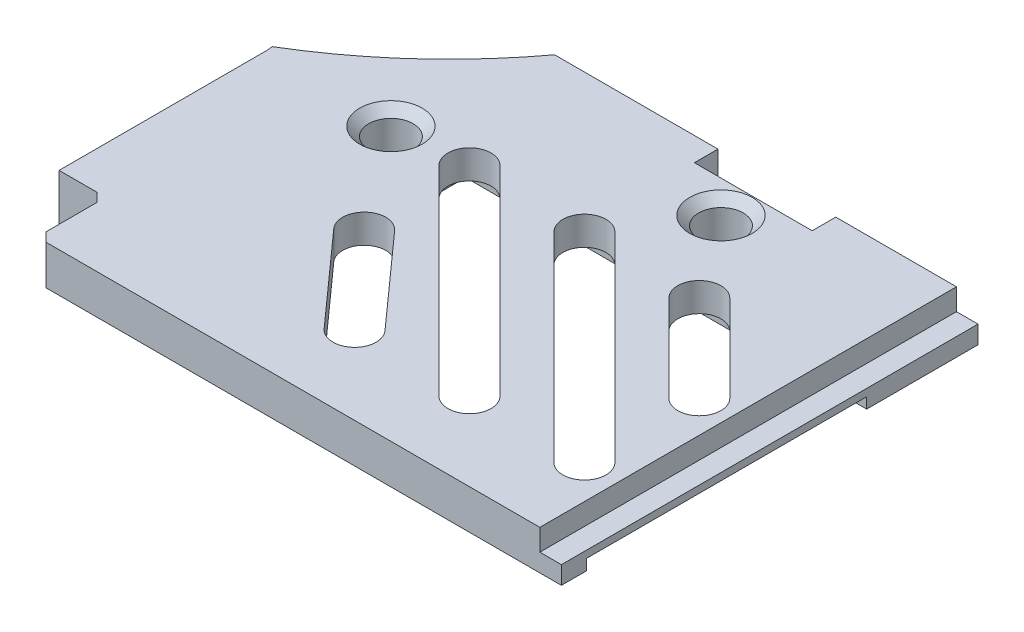
SolidWorks part; units mm, degrees
material "PPS"
ref_plane "前视基准面" through (0, 0, 0) normal (0, 0, 1) x (1, 0, 0)
ref_plane "上视基准面" through (0, 0, 0) normal (0, 1, 0) x (1, 0, 0)
ref_plane "右视基准面" through (0, 0, 0) normal (1, 0, 0) x (0, 0, -1)
sketch "基座草图-前" plane through (0, 0, 0) normal (0, 1, 0) x (1, 0, 0)
  line L2 (-24.7152, 2.0807) -> (-24.5, 0.3125)
  line L6 (-22.5, -14.2499) -> (-22.5, -7.2636)
  line L8 (-22.5, -7.2636) -> (-24.5, -7.2636)
  line L9 (-24.5, -7.2636) -> (-24.5, 0.3125)
  line L10 (-24.5, 0.3125) -> (-25.1116, 5.3379) construction
  line L12 (-26.5, 1.2398) -> (-26.5, -14.2499)
  line L13 (-26.5, -14.2499) -> (-22.5, -14.2499)
  line L16 (-4.1009, 11.812) -> (-4.1009, 8.358) construction
  line L17 (-4.1009, 8.358) -> (4.1009, 8.358)
  line L18 (4.1009, 8.358) -> (4.1009, 11.8106) construction
  line L19 (-16.253, 10) -> (-4.1009, 10)
  line L20 (-4.1009, 10) -> (-4.1009, 8.358)
  line L21 (4.1009, 8.358) -> (4.1009, 10)
  line L22 (0, 0.0001) -> (0, -23.6618) construction
  line L24 (4.1009, 10) -> (12.5, 10)
  line L25 (12.5, 10) -> (12.5, -14.2499)
  line L26 (12.5, -14.2499) -> (-26.5, -14.2499)
  arc A1 (-26.5, 2.4898) -> (-24.8662, 3.3216) centre (-28.6129, 8.6608) ccw construction
  arc A3 (-25.1116, 5.3379) -> (-57.77, 17.2644) centre (-45.4537, 0.3125) ccw construction
  arc A4 (-26.5, 1.2398) -> (-24.7152, 2.0807) centre (-28.3556, 7.493) ccw
  arc A5 (-17.503, 10) -> (-24.8662, 3.3216) centre (-44.5319, 32.4021) cw
  arc A6 (-16.253, 10) -> (-24.7152, 2.0807) centre (-44.1427, 31.321) cw
  circle A7 centre (0, 6.108) radius 1.55
  circle A8 centre (-16.866, 0) radius 1.55
  dimension "D1" = 1.25
  dimension "D2" = 1.25
  dimension "D3" = 1.25
  dimension "D4" = 16.866
  dimension "D5" = 12.5
  dimension "D6" = 9.9999
  dimension "D7" = 14.25
  dimension "D8" = 22.5
  dimension "D9" = 26.5
  dimension "D10" = 24.5
  dimension "D11" = 7.2637
extrude "基座-前" add sketch "基座草图-前" along normal blind 2.75 contours L19 A6 L2 L9 L8 L6 L26 L25 L24 L21 L17 L20 A8 A7 region at (-5.0831, 0, 2.6655)
sketch "基座草图-后" plane through (0, 0, 0) normal (0, 1, 0) x (1, 0, 0)
  line L0 (-22.5, -14.2499) -> (-22.5, -18.9999)
  line L1 (-22.5, -18.9999) -> (12.5, -18.9999)
  line L2 (12.5, -18.9999) -> (12.5, -14.2499)
  line L3 (12.5, 10) -> (12.5, -14.2499) construction
  line L4 (12.5, -14.2499) -> (-22.5, -14.2499) construction
  line L5 (-22.5, -14.2499) -> (12.5, -14.2499)
  dimension "D1" = 4.75
extrude "基座-后" add sketch "基座草图-后" along normal up to surface (2.75 mm away) up to face at (-16.866, 2.75, 1.55)
sketch "卡榫草图" plane through (0, 0, 0) normal (0, 1, 0) x (1, 0, 0)
  line L0 (-24.5, -7.2636) -> (-23.5, -7.2636)
  line L1 (-22.5, -7.2636) -> (-24.5, -7.2636) construction
  line L2 (-23.5, -7.2636) -> (-23.5, -14.2136)
  line L3 (-23.5, -14.2136) -> (-24.5, -14.2136)
  line L6 (-22.5, -18.9999) -> (-22.5, -7.2636) construction
  line L7 (-24.5, -14.2136) -> (-25.75, -14.2136)
  line L8 (-25.75, -14.2136) -> (-25.75, 0.3125)
  line L9 (-25.75, 0.3125) -> (-24.5, 0.3125) construction
  line L11 (-24.5, -7.2636) -> (-24.5, 0.3125) construction
  line L12 (-24.5, -7.2636) -> (-24.5, 0.3125)
  line L13 (-24.5, -7.2636) -> (-24.5, -14.2136)
  line L14 (-23.5, -7.2636) -> (-22.5, -7.2636)
  line L15 (-22.5, -7.2636) -> (-22.5, -14.2136)
  line L16 (-22.5, -14.2136) -> (-23.5, -14.2136)
  line L17 (-25.75, 0.3125) -> (-26.2135, 4.1214) construction
  line L18 (-24.7152, 2.0807) -> (-24.5, 0.3125) construction
  line L19 (-25.8753, 1.3423) -> (-25.75, 0.3125)
  line L20 (-24.7152, 2.0807) -> (-24.5, 0.3125)
  arc A0 (-24.7152, 2.0807) -> (-25.8753, 1.3423) centre (-44.1427, 31.321) cw
  arc A1 (-24.7152, 2.0807) -> (-16.253, 10) centre (-44.1427, 31.321) ccw construction
  dimension "D1" = 1
  dimension "D2" = 1.25
  dimension "D3" = 6.95
extrude "卡榫结构-1" add sketch "卡榫草图" along normal up to surface (2.75 mm away) contours L13 L12 L9 L8 L7 | L0 L13 L3 L2 | L12 L0 | L16 L15 L14 L2 region at (-25.1278, 0, 6.2521) region at (-24, 0, 10.7386) region at (-23, 0, 10.7386) up to face at (-16.866, 2.75, 1.55)
extrude "卡榫结构-2-注意PCB凸出部分" add sketch "草图5<4>" against normal blind 4 from surface contours L0 L13 L3 L2 | L13 L12 L9 L8 L7 region at (-25.1278, 0, 6.2521) region at (-24, 0, 10.7386) starting at face at (-9.4355, 0, 0.7086)
sketch "草图5<4>" plane through (0, 0, 0) normal (0, 1, 0) x (1, 0, 0) same geometry as "卡榫草图"
sketch "卡榫限位" plane through (0, 0, 0) normal (0, 1, 0) x (1, 0, 0)
  line L0 (12.5, 10) -> (14, 10)
  line L1 (14, 10) -> (14, -18.9999)
  line L2 (14, -18.9999) -> (12.5, -18.9999)
  line L3 (12.5, -18.9999) -> (12.5, 10)
  dimension "D1" = 1.5
extrude "限位结构" add sketch "卡榫限位" along normal blind 1.25
sketch "散热口位置" plane through (0, 0, 0) normal (0, 1, 0) x (1, 0, 0)
  line L0 (-13.916, -17.25) -> (-13.916, 2.25)
  line L1 (14, -18.9999) -> (14, 10) construction
  line L2 (-13.916, 2.25) -> (14, 2.25)
  line L4 (14, 2.25) -> (14, -17.25)
  line L5 (14, -17.25) -> (-13.916, -17.25)
  circle A0 centre (-16.866, 0) radius 1.55 construction
  dimension "D1" = 2.25
  dimension "D2" = 2.95
  dimension "D3" = 19.5
extrude "稳压PCB器件高度补偿" cut sketch "散热口位置" along normal blind 0.75
sketch "散热" plane through (0, 0.75, 0) normal (0, -1, 0) x (1, 0, 0)
  line L0 (0, 0) -> (24.2492, 0) construction
  line L1 (4.2339, -0.37) -> (10.2676, 5.6638) construction
  line L2 (3.1732, 0.6907) -> (9.2069, 6.7244)
  line L3 (5.2945, -1.4307) -> (11.3283, 4.6031)
  line L4 (-3.7661, -0.37) -> (10.1432, 13.5393) construction
  line L5 (-4.8268, 0.6907) -> (9.0825, 14.6)
  line L6 (-2.7055, -1.4307) -> (11.2038, 12.4787)
  line L7 (-11.7661, -0.37) -> (2.1432, 13.5393) construction
  line L8 (-12.8268, 0.6907) -> (1.0825, 14.6)
  line L9 (-10.7055, -1.4307) -> (3.2038, 12.4787)
  line L10 (4.2339, -0.37) -> (-3.7661, -0.37) construction
  line L11 (-3.7661, -0.37) -> (-11.7661, -0.37) construction
  line L12 (-5.8568, 13.5393) -> (-11.5554, 7.1695) construction
  line L13 (-4.7389, 12.5392) -> (-10.4375, 6.1694)
  line L14 (-6.9748, 14.5394) -> (-12.6734, 8.1696)
  line L15 (-5.8568, 13.5393) -> (2.1432, 13.5393) construction
  arc A0 (3.1732, 0.6907) -> (5.2945, -1.4307) centre (4.2339, -0.37) ccw
  arc A1 (11.3283, 4.6031) -> (9.2069, 6.7244) centre (10.2676, 5.6638) ccw
  arc A2 (-4.8268, 0.6907) -> (-2.7055, -1.4307) centre (-3.7661, -0.37) ccw
  arc A3 (11.2038, 12.4787) -> (9.0825, 14.6) centre (10.1432, 13.5393) ccw
  arc A4 (-12.8268, 0.6907) -> (-10.7055, -1.4307) centre (-11.7661, -0.37) ccw
  arc A5 (3.2038, 12.4787) -> (1.0825, 14.6) centre (2.1432, 13.5393) ccw
  arc A6 (-4.7389, 12.5392) -> (-6.9748, 14.5394) centre (-5.8568, 13.5393) ccw
  arc A7 (-12.6734, 8.1696) -> (-10.4375, 6.1694) centre (-11.5554, 7.1695) ccw
  point P5 (7.2507, 2.6469)
  point P14 (3.1885, 6.5847)
  point P20 (-4.8115, 6.5847)
  point P26 (-8.7061, 10.3544)
  dimension "D1" = 135
  dimension "D2" = 3
  dimension "D3" = 8
extrude "切除-拉伸2" cut sketch "散热" against normal through all
chamfer "倒角1" distance 0.625 angle 45 5 edges at (-16.866, 2.75, 1.55) (0, 2.75, -4.558) (-20.6617, 2.75, -5.2238) (-22.5, 1.375, 18.9999) (-22.5, 1.375, 14.2136)
sketch "草图1" plane through (0, -4, 0) normal (0, -1, 0) x (1, 0, 0)
  line L0 (-24.7152, -2.0807) -> (-24.5, -0.3125)
  line L1 (-24.5, -0.3125) -> (-24.5, 7.2636)
  line L2 (-24.5, 7.2636) -> (-23.5, 7.2636)
  line L3 (-23.5, 7.2636) -> (-23.5, 7.5136)
  line L4 (-23.5, 14.2136) -> (-23.5, 7.2636) construction
  line L5 (-23.5, 7.5136) -> (-24.75, 7.5136)
  line L8 (-24.9466, -1.9283) -> (-24.75, -0.3125)
  line L9 (-24.75, -0.3125) -> (-24.75, 7.5136)
  arc A0 (-24.7152, -2.0807) -> (-25.8753, -1.3423) centre (-44.1427, -31.321) ccw construction
  arc A1 (-24.9466, -1.9283) -> (-24.7152, -2.0807) centre (-44.1427, -31.321) cw
  point P18 (-24, 7.2636)
  dimension "D1" = 0.25
  dimension "D2" = 0.2482
  dimension "D3" = 0.25
extrude "公差切除" cut sketch "草图1" against normal up to surface (4 mm away) from surface up to face at (0, 0, -4.558) starting at face at (-24.7609, -4, 4.864)
